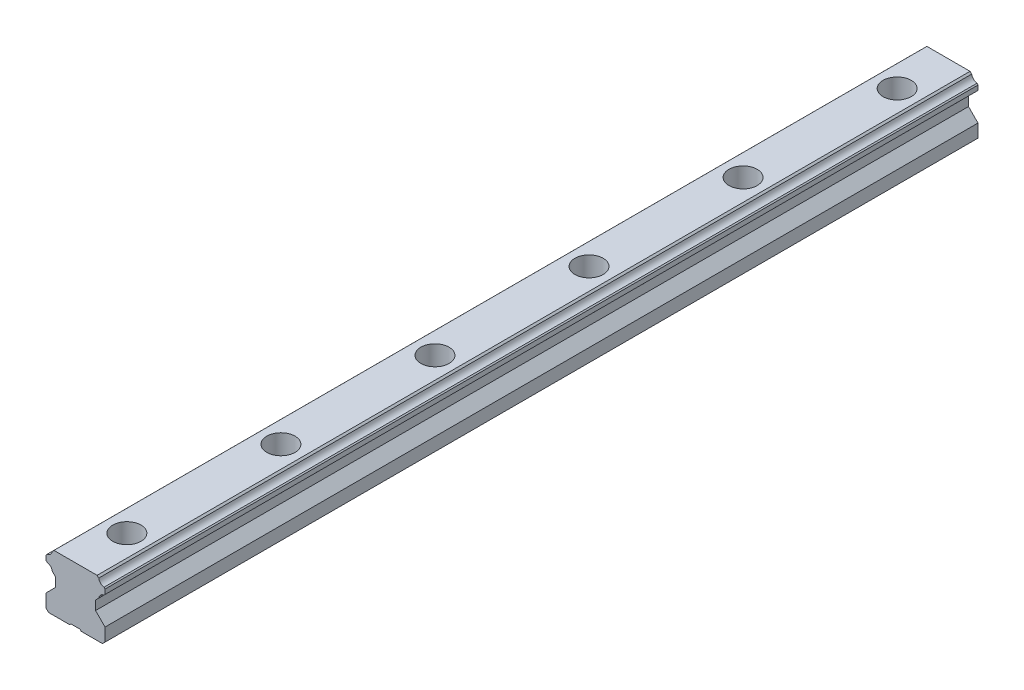
SolidWorks part; units mm, degrees
material "1060 Alloy"
ref_plane "Front Plane" through (0, 0, 0) normal (0, 0, 1) x (1, 0, 0)
ref_plane "Top Plane" through (0, 0, 0) normal (0, 1, 0) x (1, 0, 0)
ref_plane "Right Plane" through (0, 0, 0) normal (1, 0, 0) x (0, 0, -1)
sketch "Sketch1" plane through (-20, 0, 0) normal (0, 0, 1) x (1, 0, 0)
  line L0 (8.5, 18.9103) -> (8.5, 17.0793)
  line L1 (8.5, 17.0793) -> (8.9084, 16.6709)
  line L2 (10.9643, 14.613) -> (12.198, 13.3794)
  line L3 (12.198, 13.3794) -> (12.198, 9.8002)
  line L4 (12.198, 9.8002) -> (8.5, 6.1002)
  line L5 (8.5, 6.1002) -> (8.5, 1)
  line L6 (8.5, 1) -> (9.5, 0)
  line L7 (9.5, 0) -> (17.75, 0)
  line L8 (17.75, 0) -> (18.25, 0.5)
  line L9 (18.25, 0.5) -> (21.75, 0.5)
  line L10 (31.0916, 19.3308) -> (31.5, 18.9103)
  line L11 (28.4103, 22) -> (29.0357, 21.3746)
  line L12 (22.25, 0) -> (21.75, 0.5)
  line L13 (30.5, 0) -> (22.25, 0)
  line L14 (31.5, 1) -> (30.5, 0)
  line L15 (31.5, 6.1002) -> (31.5, 1)
  line L16 (27.802, 9.8002) -> (31.5, 6.1002)
  line L17 (27.802, 13.3794) -> (27.802, 9.8002)
  line L18 (29.0357, 14.613) -> (27.802, 13.3794)
  line L19 (31.5, 17.0793) -> (31.0916, 16.6709)
  line L20 (31.5, 18.9103) -> (31.5, 17.0793)
  line L21 (28.4103, 22) -> (11.5897, 22)
  line L22 (11.5897, 22) -> (10.9643, 21.3746)
  line L23 (8.9084, 19.3308) -> (8.5, 18.9103)
  line L24 (20, 22) -> (20, 0.5) construction
  line L25 (20, 0.5) -> (20, 0) construction
  arc A0 (8.9084, 16.6709) -> (10.9643, 14.613) centre (8.5153, 14.2222) cw
  arc A1 (29.0357, 21.3746) -> (31.0916, 19.3308) centre (31.4823, 21.7799) ccw
  arc A2 (31.0916, 16.6709) -> (29.0357, 14.613) centre (31.4847, 14.2222) ccw
  arc A3 (10.9643, 21.3746) -> (8.9084, 19.3308) centre (8.5177, 21.7799) cw
  dimension "D14" = 2.48
  dimension "D1" = 22
  dimension "D2" = 23
  dimension "D3" = 0.5
  dimension "D4" = 4.5
  dimension "D5" = 0.5
  dimension "D6" = 1
  dimension "D7" = 1
  dimension "D8" = 6.1002
  dimension "D9" = 9.8002
  dimension "D10" = 15.604
  dimension "D11" = 0.6254
  dimension "D12" = 3.0897
  dimension "D13" = 0.4206
  dimension "D15" = 4.9207
  dimension "D16" = 0.4084
  dimension "D17" = 7.387
  dimension "D18" = 1.2336
  dimension "D19" = 16.8205
  dimension "D20" = 0.6254
  dimension "D21" = 0.4084
extrude "Extrude1" add sketch "Sketch1" against normal blind 340
sketch "Sketch2" plane through (0, 0, 0) normal (1, 0, 0) x (0, 0, -1)
  line L0 (20, 22) -> (25.5, 22)
  line L1 (25.5, 22) -> (25.5, 13)
  line L2 (25.5, 13) -> (23.5, 13)
  line L3 (23.5, 13) -> (23.5, 0)
  line L4 (23.5, 0) -> (20, 0)
  line L5 (20, 0) -> (20, 22) construction
  line L6 (20, 0) -> (20, 22) construction
  line L7 (20, 22) -> (20, 0)
  line L8 (340, 0) -> (0, 0) construction
  line L9 (340, 22) -> (0, 22) construction
  dimension "D1" = 11
  dimension "D2" = 7
  dimension "D3" = 9
  dimension "D4" = 20
revolve "Cut-Revolve1" cut sketch "Sketch2" angle 360 about L6 reverse direction yes
ref_axis "Axis1" through (0, 0, -231) along (0, 0, 1)
pattern_linear "LPattern1" count 6 spacing 60 along (0, 0, -1) of "Cut-Revolve1"
